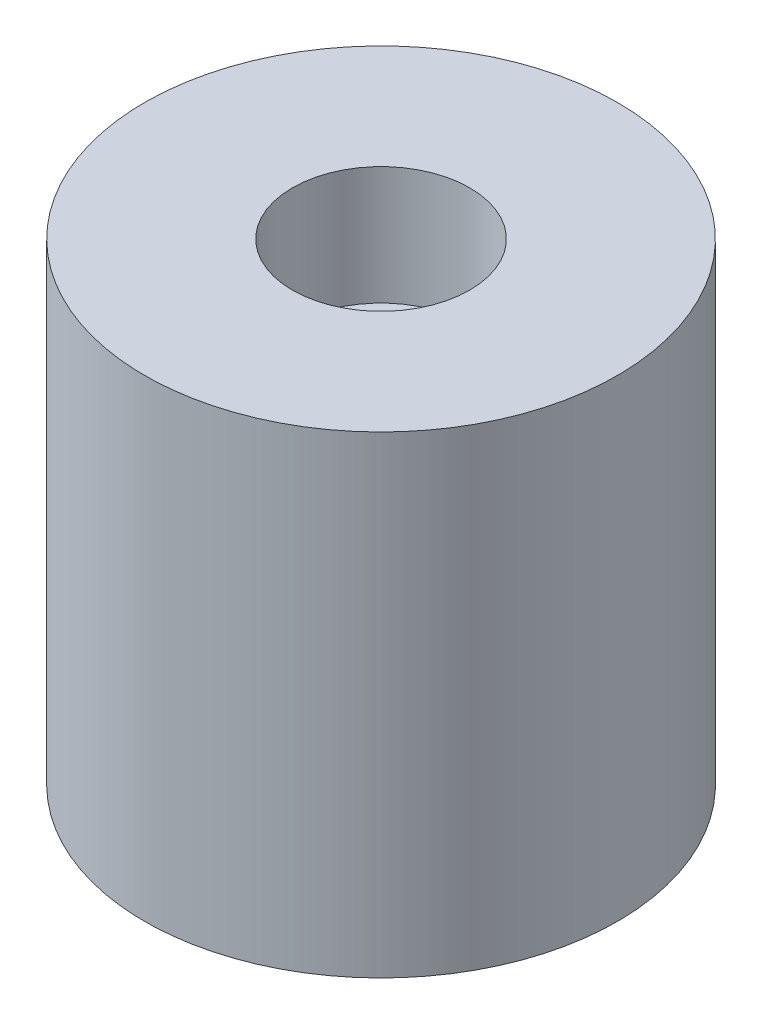
SolidWorks part; units mm, degrees
ref_plane "Front Plane" through (0, 0, 0) normal (0, 0, 1) x (1, 0, 0)
ref_plane "Top Plane" through (0, 0, 0) normal (0, 1, 0) x (1, 0, 0)
ref_plane "Right Plane" through (0, 0, 0) normal (1, 0, 0) x (0, 0, -1)
sketch "Sketch2" plane through (0, 0, 0) normal (0, 0, 1) x (1, 0, 0)
  line L0 (0, 0) -> (0, 9.525) construction
  line L1 (1.9844, -12.7) -> (12.7, -12.7)
  line L2 (1.9844, -12.7) -> (1.9844, 12.7)
  line L3 (1.9844, 12.7) -> (12.7, 12.7)
  line L4 (12.7, -12.7) -> (12.7, 12.7)
  line L6 (1.9844, 12.7) -> (4.7625, 12.7)
  line L7 (1.9844, 12.7) -> (1.9844, 6.35)
  line L8 (1.9844, 6.35) -> (4.7625, 6.35)
  line L9 (4.7625, 12.7) -> (4.7625, 6.35)
  point P8 (1.9844, 0)
  dimension "D1" = 12.7
  dimension "D2" = 1.9844
  dimension "D3" = 25.4
  dimension "D4" = 4.7625
  dimension "D5" = 19.05
revolve "Revolve1" add sketch "Sketch2" angle 360 about L0 region at (7.6172, -0.6601, 0)
